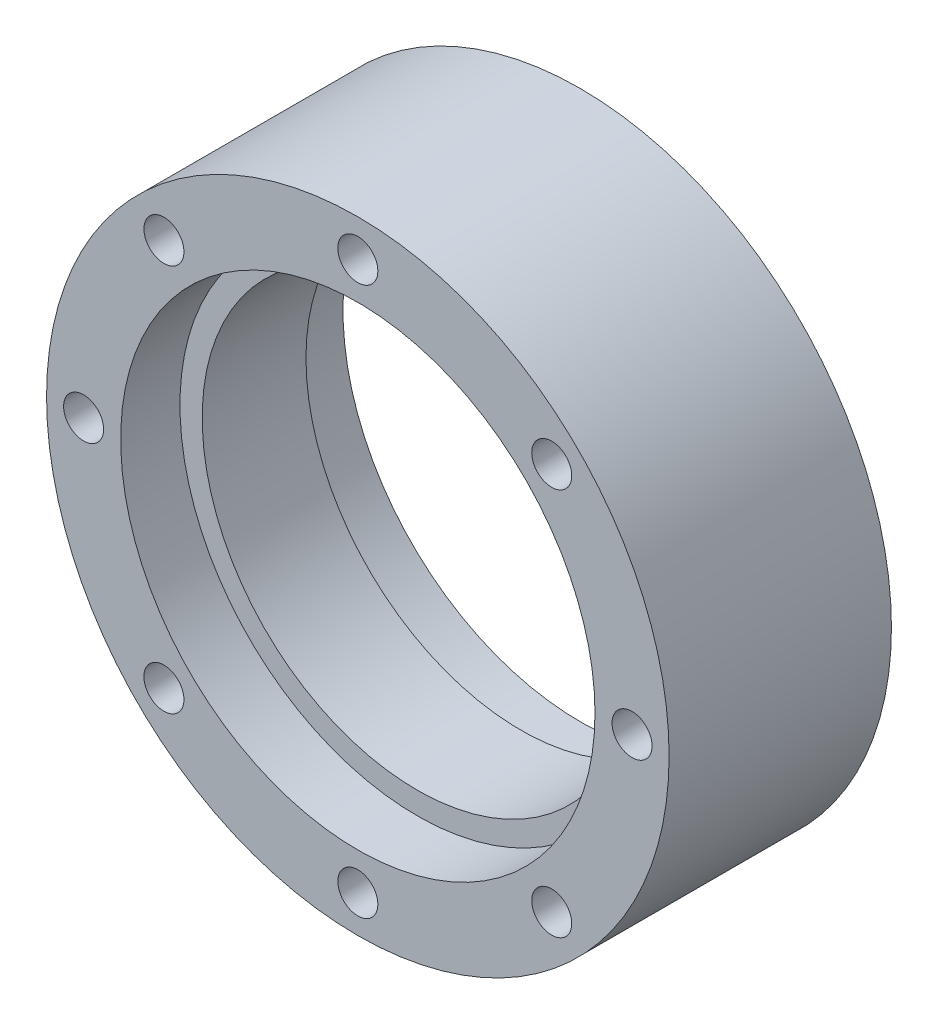
SolidWorks part; units mm, degrees
ref_plane "Front Plane" through (0, 0, 0) normal (0, 0, 1) x (1, 0, 0)
ref_plane "Top Plane" through (0, 0, 0) normal (0, 1, 0) x (1, 0, 0)
ref_plane "Right Plane" through (0, 0, 0) normal (1, 0, 0) x (0, 0, -1)
ref_axis "Z" through (0, 0, 8.25) along (0, 0, -1)
sketch "Sketch1" plane through (0, 0, 0) normal (0, 0, 1) x (1, 0, 0)
  circle A0 centre (0, 0) radius 21
  circle A1 centre (0, 0) radius 14.5
  dimension "D1" = 29
  dimension "D2" = 42
extrude "MainBody" add sketch "Sketch1" along normal blind 7.5 and the other way blind 7.5
sketch "Sketch2" plane through (0, 0, 7.5) normal (0, 0, 1) x (1, 0, 0)
  circle A0 centre (0, 0) radius 16
  dimension "D1" = 32
extrude "Cut-Extrude1" cut sketch "Sketch2" against normal blind 4
mirror "Mirror1" about plane through (0, 0, 0) normal (0, 0, 1) of "Cut-Extrude1"
sketch "Sketch3" plane through (0, 0, 0) normal (0, 0, 1) x (1, 0, 0)
  line L1 (0, 21) -> (0, 16) construction
  circle A0 centre (0, 18.5) radius 1.35
  circle A2 centre (0, 0) radius 21 construction
  circle A3 centre (0, 0) radius 16 construction
  circle A4 centre (0, 0) radius 18.5 construction
  dimension "D1" = 2.7
  dimension "D2" = 32
  dimension "D3" = 37
extrude "Cut-Extrude2" cut sketch "Sketch3" against normal through all both and the other way through all
sketch "Sketch4" plane through (0, 0, -7.5) normal (0, 0, -1) x (-1, 0, 0)
  circle A0 centre (0, 18.5) radius 2.25
  circle A1 centre (0, 18.5) radius 1.35 construction
  dimension "D1" = 4.5
extrude "Cut-Extrude4" cut sketch "Sketch4" against normal blind 2.5 and the other way through all
chamfer "Chamfer1" distance 0.1 angle 45 1 edges at (-1.35, 18.5, -5)
pattern_circular "CirPattern1" count 4 over 360 about axis through (0, 0, 8.25) along (0, 0, -1) of "Cut-Extrude2", "Cut-Extrude4", "Chamfer1"
pattern_circular "CirPattern2" count 8 over 360 about axis through (0, 0, 8.25) along (0, 0, -1) of "Cut-Extrude2"
equation "\"BearingBaseDistance\"= 7"
equation "\"BearingOD\"= 32"
equation "\"BearingHeight\"= 4"
equation "\"D1@Cut-Extrude1\"=\"BearingHeight\""
equation "\"D1@MainBody\" = \"BearingBaseDistance\" / 2 + \"BearingHeight\""
equation "\"D2@MainBody\" = \"BearingBaseDistance\" / 2 + \"BearingHeight\""
equation "\"D1@Sketch1\"=\"BearingOD\"-3"
equation "\"D1@Sketch2\"=\"BearingOD\""
equation "\"SeatsOD\"= \"BearingOD\" + 10"
equation "\"D2@Sketch1\"=\"SeatsOD\""
equation "\"D2@Sketch3\"=\"BearingOD\""
